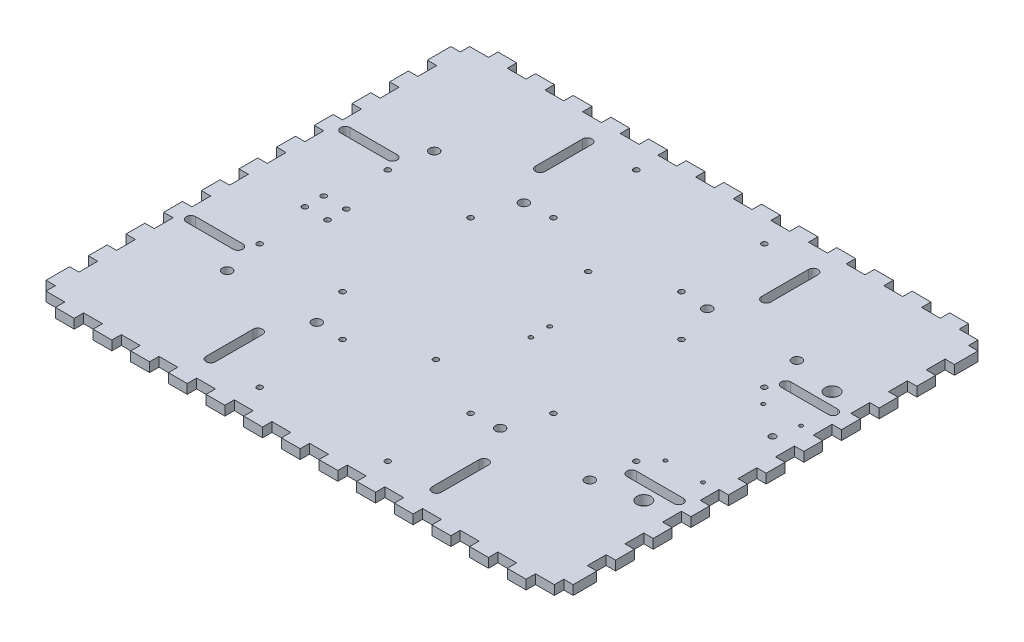
SolidWorks part; units mm, degrees
material "Acrylic (Medium-high impact)"
ref_plane "Front Plane" through (0, 0, 0) normal (0, 0, 1) x (1, 0, 0)
ref_plane "Top Plane" through (0, 0, 0) normal (0, 1, 0) x (1, 0, 0)
ref_plane "Right Plane" through (0, 0, 0) normal (1, 0, 0) x (0, 0, -1)
sketch "Sketch1" plane through (0, 0, 0) normal (0, 1, 0) x (1, 0, 0)
  line L0 (0, -51.3715) -> (0, 51.3715) construction
  line L5 (-177.8, -149.225) -> (177.8, -149.225)
  line L6 (-177.8, -149.225) -> (-177.8, 149.225)
  line L11 (-177.8, 149.225) -> (177.8, 149.225)
  line L13 (177.8, -149.225) -> (177.8, 149.225)
  line L14 (-177.8, -149.225) -> (177.8, 149.225) construction
  line L15 (-177.8, 149.225) -> (177.8, -149.225) construction
  circle A1 centre (0, 51.3715) radius 1.778
  circle A2 centre (0, -51.3715) radius 1.778
  point P0 (0, 0)
  point P13 (0, 0)
  dimension "D4" = 3.556
  dimension "D1" = 355.6
  dimension "D2" = 298.45
  dimension "D3" = 102.743
extrude "Boss-Extrude1" add sketch "Sketch1" along normal blind 6.35
sketch "Sketch2" plane through (0, 6.35, 0) normal (0, 1, 0) x (1, 0, 0)
  line L0 (-61.8382, 69.85) -> (-122.3118, 69.85) construction
  line L1 (0, 0) -> (-61.8382, 0) construction
  line L2 (-61.8382, 0) -> (-61.8382, 69.85) construction
  line L4 (-61.8382, 0) -> (-61.8382, -69.85) construction
  line L5 (-61.8382, -69.85) -> (-122.3118, -69.85) construction
  line L6 (-61.8382, 69.85) -> (61.8382, 69.85) construction
  line L7 (-61.8382, -69.85) -> (61.8382, -69.85) construction
  line L8 (122.3118, 69.85) -> (61.8382, 69.85) construction
  line L9 (122.3118, -69.85) -> (61.8382, -69.85) construction
  line L10 (61.8382, 69.85) -> (61.8382, 0) construction
  line L11 (61.8382, 0) -> (61.8382, -69.85) construction
  line L12 (0, 0) -> (61.8382, 0) construction
  circle A8 centre (61.8382, -69.85) radius 3.2385
  circle A9 centre (122.3118, -69.85) radius 3.2385
  circle A10 centre (-122.3118, -69.85) radius 3.2385
  circle A11 centre (-61.8382, -69.85) radius 3.2385
  circle A12 centre (-122.3118, 69.85) radius 3.2385
  circle A13 centre (-61.8382, 69.85) radius 3.2385
  circle A14 centre (61.8382, 69.85) radius 3.2385
  circle A15 centre (122.3118, 69.85) radius 3.2385
  dimension "D4" = 6.477
  dimension "D1" = 69.85
  dimension "D2" = 61.8382
  dimension "D3" = 60.4736
extrude "Cut-Extrude1" cut sketch "Sketch2" against normal through all from surface starting at face at (0, 6.35, 0)
sketch "Sketch8" plane through (0, 6.35, 0) normal (0, 1, 0) x (1, 0, 0)
  line L0 (0, 0) -> (0, 63.5) construction
  line L1 (0, 63.5) -> (152.4, 63.5) construction
  line L2 (-149.4967, 0) -> (149.4967, 0) construction
  circle A1 centre (152.4, 63.5) radius 4.7625
  circle A2 centre (152.4, -63.5) radius 4.7625
  point P7 (0, 0)
  dimension "D1" = 63.5
  dimension "D3" = 9.525
  dimension "D2" = 152.4
extrude "Cut-Extrude5" cut sketch "Sketch8" against normal through all
ref_plane "Plane1" through (0, 0, -2.1167) normal (0, 0, 1) x (1, 0, 0)
sketch "Sketch15" plane through (0, 6.35, 0) normal (0, 1, 0) x (1, 0, 0)
  line L1 (146.05, 168.275) -> (133.35, 168.275)
  line L2 (146.05, 168.275) -> (146.05, 142.875)
  line L3 (146.05, 142.875) -> (133.35, 142.875)
  line L4 (133.35, 168.275) -> (133.35, 142.875)
  line L5 (146.05, 168.275) -> (133.35, 142.875) construction
  line L6 (146.05, 142.875) -> (133.35, 168.275) construction
  line L8 (120.65, 168.275) -> (107.95, 168.275)
  line L9 (120.65, 168.275) -> (120.65, 142.875)
  line L10 (120.65, 142.875) -> (107.95, 142.875)
  line L11 (107.95, 168.275) -> (107.95, 142.875)
  line L12 (120.65, 168.275) -> (107.95, 142.875) construction
  line L13 (120.65, 142.875) -> (107.95, 168.275) construction
  line L14 (95.25, 168.275) -> (82.55, 168.275)
  line L15 (95.25, 168.275) -> (95.25, 142.875)
  line L16 (95.25, 142.875) -> (82.55, 142.875)
  line L17 (82.55, 168.275) -> (82.55, 142.875)
  line L18 (95.25, 168.275) -> (82.55, 142.875) construction
  line L19 (95.25, 142.875) -> (82.55, 168.275) construction
  line L20 (69.85, 168.275) -> (57.15, 168.275)
  line L21 (69.85, 168.275) -> (69.85, 142.875)
  line L22 (69.85, 142.875) -> (57.15, 142.875)
  line L23 (57.15, 168.275) -> (57.15, 142.875)
  line L24 (69.85, 168.275) -> (57.15, 142.875) construction
  line L25 (69.85, 142.875) -> (57.15, 168.275) construction
  line L26 (44.45, 168.275) -> (31.75, 168.275)
  line L27 (44.45, 168.275) -> (44.45, 142.875)
  line L28 (44.45, 142.875) -> (31.75, 142.875)
  line L29 (31.75, 168.275) -> (31.75, 142.875)
  line L30 (44.45, 168.275) -> (31.75, 142.875) construction
  line L31 (44.45, 142.875) -> (31.75, 168.275) construction
  line L32 (19.05, 168.275) -> (6.35, 168.275)
  line L33 (19.05, 168.275) -> (19.05, 142.875)
  line L34 (19.05, 142.875) -> (6.35, 142.875)
  line L35 (6.35, 168.275) -> (6.35, 142.875)
  line L36 (19.05, 168.275) -> (6.35, 142.875) construction
  line L37 (19.05, 142.875) -> (6.35, 168.275) construction
  line L38 (-6.35, 168.275) -> (-19.05, 168.275)
  line L39 (-6.35, 168.275) -> (-6.35, 142.875)
  line L40 (-6.35, 142.875) -> (-19.05, 142.875)
  line L41 (-19.05, 168.275) -> (-19.05, 142.875)
  line L42 (-6.35, 168.275) -> (-19.05, 142.875) construction
  line L43 (-6.35, 142.875) -> (-19.05, 168.275) construction
  line L44 (-31.75, 168.275) -> (-44.45, 168.275)
  line L45 (-31.75, 168.275) -> (-31.75, 142.875)
  line L46 (-31.75, 142.875) -> (-44.45, 142.875)
  line L47 (-44.45, 168.275) -> (-44.45, 142.875)
  line L48 (-31.75, 168.275) -> (-44.45, 142.875) construction
  line L49 (-31.75, 142.875) -> (-44.45, 168.275) construction
  line L50 (-57.15, 168.275) -> (-69.85, 168.275)
  line L51 (-57.15, 168.275) -> (-57.15, 142.875)
  line L52 (-57.15, 142.875) -> (-69.85, 142.875)
  line L53 (-69.85, 168.275) -> (-69.85, 142.875)
  line L54 (-57.15, 168.275) -> (-69.85, 142.875) construction
  line L55 (-57.15, 142.875) -> (-69.85, 168.275) construction
  line L56 (-82.55, 168.275) -> (-95.25, 168.275)
  line L57 (-82.55, 168.275) -> (-82.55, 142.875)
  line L58 (-82.55, 142.875) -> (-95.25, 142.875)
  line L59 (-95.25, 168.275) -> (-95.25, 142.875)
  line L60 (-82.55, 168.275) -> (-95.25, 142.875) construction
  line L61 (-82.55, 142.875) -> (-95.25, 168.275) construction
  line L62 (-107.95, 168.275) -> (-120.65, 168.275)
  line L63 (-107.95, 168.275) -> (-107.95, 142.875)
  line L64 (-107.95, 142.875) -> (-120.65, 142.875)
  line L65 (-120.65, 168.275) -> (-120.65, 142.875)
  line L66 (-107.95, 168.275) -> (-120.65, 142.875) construction
  line L67 (-107.95, 142.875) -> (-120.65, 168.275) construction
  line L68 (-133.35, 168.275) -> (-146.05, 168.275)
  line L69 (-133.35, 168.275) -> (-133.35, 142.875)
  line L70 (-133.35, 142.875) -> (-146.05, 142.875)
  line L71 (-146.05, 168.275) -> (-146.05, 142.875)
  line L72 (-133.35, 168.275) -> (-146.05, 142.875) construction
  line L73 (-133.35, 142.875) -> (-146.05, 168.275) construction
  line L79 (177.8, -149.225) -> (177.8, 149.225) construction
  line L84 (184.15, 168.275) -> (158.75, 168.275)
  line L85 (184.15, 168.275) -> (184.15, 142.875)
  line L90 (184.15, 142.875) -> (158.75, 142.875)
  line L91 (158.75, 168.275) -> (158.75, 142.875)
  line L96 (184.15, 168.275) -> (158.75, 142.875) construction
  line L97 (184.15, 142.875) -> (158.75, 168.275) construction
  line L102 (-184.15, 168.275) -> (-158.75, 168.275)
  line L103 (-184.15, 168.275) -> (-184.15, 142.875)
  line L108 (-184.15, 142.875) -> (-158.75, 142.875)
  line L109 (-158.75, 168.275) -> (-158.75, 142.875)
  line L114 (-184.15, 168.275) -> (-158.75, 142.875) construction
  line L115 (-184.15, 142.875) -> (-158.75, 168.275) construction
  line L120 (177.8, 149.225) -> (-177.8, 149.225) construction
  line L121 (-177.8, 149.225) -> (-177.8, -149.225) construction
  line L165 (-158.75, 168.275) -> (-171.45, 168.275) [skipped]
  line L166 (-158.75, 168.275) -> (-158.75, 142.875) [skipped]
  line L167 (-158.75, 142.875) -> (-171.45, 142.875) [skipped]
  line L168 (-171.45, 168.275) -> (-171.45, 142.875) [skipped]
  line L169 (-184.15, 168.275) -> (-196.85, 168.275) [skipped]
  line L170 (-184.15, 168.275) -> (-184.15, 142.875) [skipped]
  line L171 (-184.15, 142.875) -> (-196.85, 142.875) [skipped]
  line L172 (-196.85, 168.275) -> (-196.85, 142.875) [skipped]
  line L173 (-158.75, 168.275) -> (-171.45, 142.875) construction
  line L174 (-158.75, 142.875) -> (-171.45, 168.275) construction
  line L175 (-184.15, 168.275) -> (-196.85, 142.875) construction
  line L176 (-184.15, 142.875) -> (-196.85, 168.275) construction
  point P0 (139.7, 155.575)
  point P9 (-190.5, 155.575)
  point P10 (-165.1, 155.575)
  point P11 (114.3, 155.575)
  point P16 (88.9, 155.575)
  point P21 (63.5, 155.575)
  point P26 (38.1, 155.575)
  point P31 (12.7, 155.575)
  point P36 (-12.7, 155.575)
  point P41 (-38.1, 155.575)
  point P46 (-63.5, 155.575)
  point P51 (-88.9, 155.575)
  point P56 (-114.3, 155.575)
  point P61 (-139.7, 155.575)
  point P68 (171.45, 155.575)
  point P73 (-171.45, 155.575)
  dimension "D2" = 12.7
  dimension "D3" = 12.7
  dimension "D4" = 25.4
  dimension "D6" = 19.05
  dimension "D7" = 19.05
  dimension "D8" = 6.35
  dimension "D9" = 25.4
  dimension "D10" = 25.4
  dimension "D11" = 6.35
  dimension "D12" = 31.75
  dimension "D13" = 25.4
  dimension "D14" = 25.4
  dimension "D15" = 6.35
  dimension "D16" = 6.35
  dimension "D5" = 14
sketch "Sketch16" plane through (0, 6.35, 0) normal (0, 1, 0) x (1, 0, 0)
  line L1 (196.85, 120.65) -> (171.45, 120.65)
  line L2 (196.85, 120.65) -> (196.85, 107.95)
  line L3 (196.85, 107.95) -> (171.45, 107.95)
  line L4 (171.45, 120.65) -> (171.45, 107.95)
  line L5 (196.85, 120.65) -> (171.45, 107.95) construction
  line L6 (196.85, 107.95) -> (171.45, 120.65) construction
  line L8 (177.8, -149.225) -> (177.8, 149.225) construction
  line L9 (177.8, 149.225) -> (-177.8, 149.225) construction
  point P0 (184.15, 114.3)
  dimension "D1" = 6.35
  dimension "D2" = 28.575
  dimension "D3" = 12.7
  dimension "D4" = 25.4
extrude "Cut-Extrude19" cut sketch "Sketch16" against normal through all and the other way through all
pattern_linear "LPattern2" count 10 spacing 25.4 along (0, 0, 1) of "Cut-Extrude19"
mirror "Mirror4" about plane through (0, 0, 0) normal (1, 0, 0) of "Cut-Extrude19", "LPattern2"
sketch "Sketch18" plane through (0, 6.35, 0) normal (0, 1, 0) x (1, 0, 0)
  line L1 (196.85, 161.925) -> (171.45, 161.925)
  line L2 (196.85, 161.925) -> (196.85, 136.525)
  line L3 (196.85, 136.525) -> (171.45, 136.525)
  line L4 (171.45, 161.925) -> (171.45, 136.525)
  line L5 (196.85, 161.925) -> (171.45, 136.525) construction
  line L6 (196.85, 136.525) -> (171.45, 161.925) construction
  line L8 (0, -55) -> (0, 55) construction
  line L9 (-196.85, 136.525) -> (-171.45, 161.925) construction
  line L10 (-196.85, 161.925) -> (-171.45, 136.525) construction
  line L11 (-171.45, 161.925) -> (-171.45, 136.525)
  line L12 (-196.85, 136.525) -> (-171.45, 136.525)
  line L13 (-196.85, 161.925) -> (-196.85, 136.525)
  line L14 (-196.85, 161.925) -> (-171.45, 161.925)
  line L15 (-55, 0) -> (55, 0) construction
  line L16 (196.85, -136.525) -> (171.45, -161.925) construction
  line L17 (196.85, -161.925) -> (171.45, -136.525) construction
  line L18 (171.45, -161.925) -> (171.45, -136.525)
  line L19 (196.85, -136.525) -> (171.45, -136.525)
  line L20 (196.85, -161.925) -> (196.85, -136.525)
  line L21 (196.85, -161.925) -> (171.45, -161.925)
  line L22 (-196.85, -161.925) -> (-171.45, -136.525) construction
  line L23 (-196.85, -136.525) -> (-171.45, -161.925) construction
  line L24 (-196.85, -161.925) -> (-171.45, -161.925)
  line L25 (-196.85, -161.925) -> (-196.85, -136.525)
  line L26 (-196.85, -136.525) -> (-171.45, -136.525)
  line L27 (-171.45, -161.925) -> (-171.45, -136.525)
  line L28 (177.8, 149.225) -> (-177.8, 149.225) construction
  line L29 (177.8, 120.65) -> (177.8, 149.225) construction
  point P0 (184.15, 149.225)
  point P15 (-184.15, 149.225)
  point P22 (184.15, -149.225)
  point P27 (-184.15, -149.225)
  dimension "D1" = 12.7
  dimension "D2" = 6.35
  dimension "D3" = 25.4
  dimension "D4" = 25.4
extrude "Cut-Extrude21" cut sketch "Sketch18" against normal through all
extrude "Cut-Extrude22" cut sketch "Sketch15" against normal through all
mirror "Mirror5" about plane through (0, 0, 0) normal (0, 0, 1) of "Cut-Extrude22"
sketch "Sketch19" plane through (0, 6.35, 0) normal (0, 1, 0) x (1, 0, 0)
  line L0 (0, 0) -> (0, 99.06) construction
  line L1 (0, 99.06) -> (0, 130.81) construction
  line L2 (-46.99, 67.31) -> (46.99, 67.31) construction
  line L3 (-46.99, 67.31) -> (-46.99, 130.81) construction
  line L4 (-46.99, 130.81) -> (46.99, 130.81) construction
  line L5 (46.99, 67.31) -> (46.99, 130.81) construction
  line L6 (-46.99, 67.31) -> (46.99, 130.81) construction
  line L7 (-46.99, 130.81) -> (46.99, 67.31) construction
  line L8 (0, 99.06) -> (-46.99, 99.06) construction
  circle A0 centre (-43.18, 127) radius 1.8415
  circle A1 centre (43.18, 127) radius 1.8415
  circle A2 centre (43.18, 71.12) radius 1.8415
  circle A3 centre (-43.18, 71.12) radius 1.8415
  dimension "D5" = 3.81
  dimension "D6" = 3.683
  dimension "D1" = 99.06
  dimension "D2" = 63.5
  dimension "D3" = 93.98
  dimension "D4" = 3.81
extrude "Cut-Extrude23" cut sketch "Sketch19" against normal through all
mirror "Mirror6" about plane through (0, 0, 0) normal (0, 0, 1) of "Cut-Extrude23"
ref_axis "Axis1" through (0, 6.6675, 0) along (0, -1, 0)
pattern_circular "CirPattern1" count 4 every 90 about axis through (0, 6.6675, 0) along (0, -1, 0) skipping 2 of "Cut-Extrude23"
sketch "Sketch20" plane through (0, 6.35, 0) normal (0, 1, 0) x (1, 0, 0)
  line L0 (132.715, -52.07) -> (164.465, -52.07) construction
  line L1 (132.715, -48.895) -> (164.465, -48.895)
  line L2 (132.715, -55.245) -> (164.465, -55.245)
  line L3 (171.45, -95.25) -> (171.45, -82.55) construction
  arc A0 (132.715, -48.895) -> (132.715, -55.245) centre (132.715, -52.07) ccw
  arc A1 (164.465, -55.245) -> (164.465, -48.895) centre (164.465, -52.07) ccw
  circle A3 centre (122.3118, -69.85) radius 3.2385 construction
  point P2 (148.59, -52.07)
  dimension "D4" = 17.78
  dimension "D1" = 6.35
  dimension "D2" = 31.75
  dimension "D3" = 6.985
extrude "Cut-Extrude24" cut sketch "Sketch20" against normal through all
mirror "Mirror7" about plane through (0, 0, 0) normal (0, 0, 1) of "Cut-Extrude24"
sketch "Sketch21" plane through (0, 6.35, 0) normal (0, 1, 0) x (1, 0, 0)
  circle A0 centre (161.8478, -32.9559) radius 1.27 construction
  circle A1 centre (136.4478, -32.9617) radius 1.27 construction
  circle A2 centre (161.8329, 33.0841) radius 1.27 construction
  circle A3 centre (158.4215, 17.2833) radius 2.2225 construction
  circle A4 centre (136.4329, 33.0783) radius 1.27 construction
  circle A5 centre (161.8478, -32.9559) radius 1.27
  circle A6 centre (136.4478, -32.9617) radius 1.27
  circle A7 centre (161.8329, 33.0841) radius 1.27
  circle A8 centre (158.4215, 17.2833) radius 2.2225
  circle A9 centre (136.4329, 33.0783) radius 1.27
extrude "Cut-Extrude25" cut sketch "Sketch21" against normal through all
mirror "Mirror8" about plane through (0, 0, 0) normal (1, 0, 0) of "Mirror7"
sketch "Sketch23" plane through (0, 6.35, 0) normal (0, 1, 0) x (1, 0, 0)
  circle A0 centre (19.05, -6.35) radius 1.4224 construction
  circle A1 centre (19.05, 6.35) radius 1.4224 construction
  circle A2 centre (19.05, -6.35) radius 1.4224
  circle A3 centre (19.05, 6.35) radius 1.4224
extrude "Cut-Extrude27" cut sketch "Sketch23" against normal through all
sketch "Sketch24" plane through (0, 6.35, 0) normal (0, 1, 0) x (1, 0, 0)
  point P0 (19.05, 6.35)
  point P1 (19.05, -6.35)
sketch "Sketch26" plane through (0, 6.35, 0) normal (0, 1, 0) x (1, 0, 0)
  line L0 (177.8, 0) -> (-177.8, 0) construction
  line L1 (177.8, -6.35) -> (177.8, 6.35) construction
  line L2 (-177.8, 6.35) -> (-177.8, -6.35) construction
  line L3 (-76.2, -95.25) -> (-76.2, -127) construction
  line L4 (-73.025, -95.25) -> (-73.025, -127)
  line L5 (-79.375, -95.25) -> (-79.375, -127)
  line L6 (-171.45, 6.35) -> (-171.45, 19.05) construction
  line L7 (76.2, -95.25) -> (76.2, -127) construction
  line L8 (79.375, -95.25) -> (79.375, -127)
  line L9 (73.025, -95.25) -> (73.025, -127)
  line L10 (-177.8, -95.25) -> (-177.8, -107.95) construction
  line L11 (177.8, -107.95) -> (177.8, -95.25) construction
  line L12 (-107.95, -149.225) -> (-95.25, -149.225) construction
  line L14 (-76.2, 95.25) -> (-76.2, 127) construction
  line L15 (-73.025, 95.25) -> (-73.025, 127)
  line L16 (-79.375, 95.25) -> (-79.375, 127)
  line L17 (76.2, 95.25) -> (76.2, 127) construction
  line L18 (79.375, 95.25) -> (79.375, 127)
  line L19 (73.025, 95.25) -> (73.025, 127)
  circle A2 centre (-118.11, 6.35) radius 1.8415
  circle A3 centre (-118.11, -6.35) radius 1.8415
  circle A4 centre (-133.35, 6.35) radius 1.8415
  circle A5 centre (-133.35, -6.35) radius 1.8415
  arc A6 (-73.025, -95.25) -> (-79.375, -95.25) centre (-76.2, -95.25) ccw
  arc A7 (-79.375, -127) -> (-73.025, -127) centre (-76.2, -127) ccw
  arc A9 (79.375, -95.25) -> (73.025, -95.25) centre (76.2, -95.25) ccw
  arc A10 (73.025, -127) -> (79.375, -127) centre (76.2, -127) ccw
  arc A11 (-73.025, 95.25) -> (-79.375, 95.25) centre (-76.2, 95.25) cw
  arc A12 (-79.375, 127) -> (-73.025, 127) centre (-76.2, 127) cw
  arc A13 (79.375, 95.25) -> (73.025, 95.25) centre (76.2, 95.25) cw
  arc A14 (73.025, 127) -> (79.375, 127) centre (76.2, 127) cw
  point P18 (-76.2, -111.125)
  point P27 (76.2, -111.125)
  point P42 (-76.2, 111.125)
  point P49 (76.2, 111.125)
  dimension "D1" = 3.683
  dimension "D8" = 31.75
  dimension "D2" = 6.35
  dimension "D3" = 6.35
  dimension "D4" = 6.35
  dimension "D5" = 6.35
  dimension "D6" = 15.24
  dimension "D7" = 6.35
  dimension "D9" = 101.6
  dimension "D10" = 101.6
  dimension "D11" = 38.1
  dimension "D12" = 6.35
  dimension "D13" = 31.75
  dimension "D14" = 38.1
extrude "Cut-Extrude28" cut sketch "Sketch26" against normal through all
